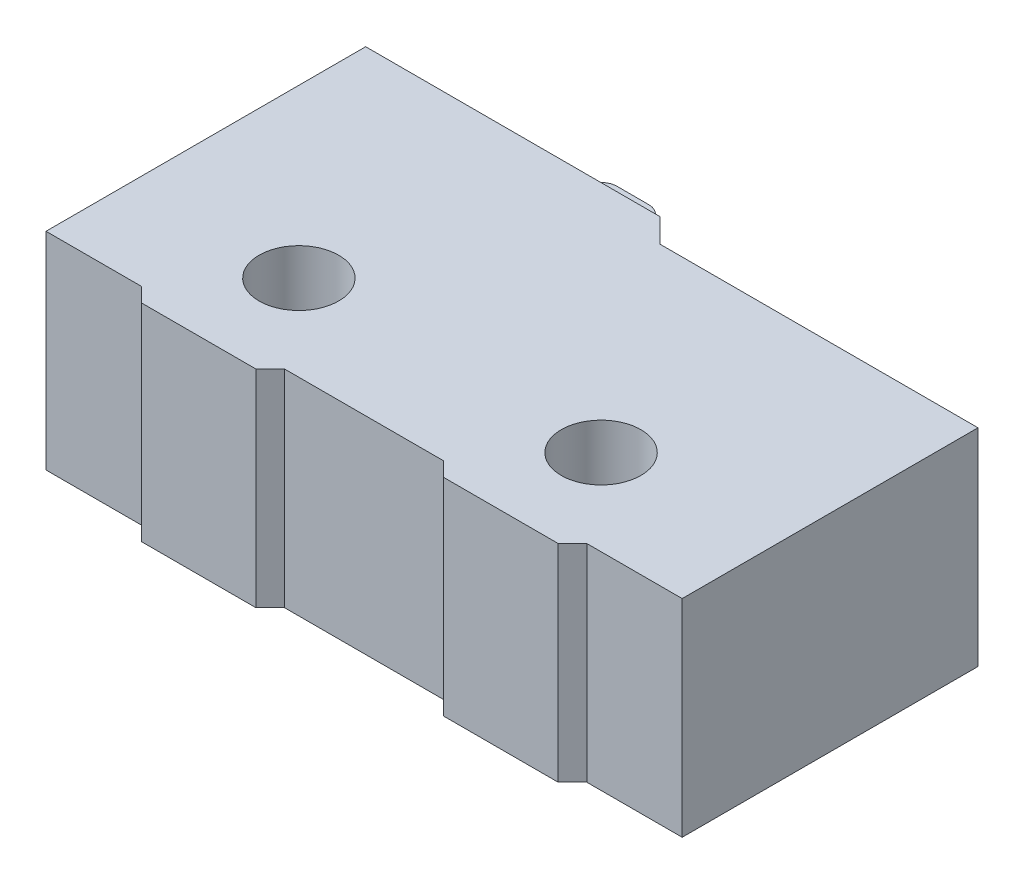
SolidWorks part; units mm, degrees
ref_plane "Front Plane" through (0, 0, 0) normal (0, 0, 1) x (1, 0, 0)
ref_plane "Top Plane" through (0, 0, 0) normal (0, 1, 0) x (1, 0, 0)
ref_plane "Right Plane" through (0, 0, 0) normal (1, 0, 0) x (0, 0, -1)
sketch "스케치1" plane through (0, 0, 0) normal (0, 1, 0) x (1, 0, 0)
  line L1 (-10, 5.25) -> (10, 5.25)
  line L2 (-10, 5.25) -> (-10, -5.25)
  line L3 (-10, -5.25) -> (10, -5.25)
  line L4 (10, 5.25) -> (10, -5.25)
  dimension "D1" = 20
  dimension "D2" = 10.5
  dimension "D3" = 10
  dimension "D4" = 5.25
extrude "보스-돌출1" add sketch "스케치1" along normal blind 6.5
sketch "스케치2" plane through (0, 6.5, 0) normal (0, 1, 0) x (1, 0, 0)
  line L0 (-11.4248, -2.1) -> (49988.5752, -2.1) construction
  line L1 (-4.75, -0.1929) -> (-4.75, -50000.1929) construction
  line L2 (4.75, 1.0289) -> (4.75, -49998.9711) construction
  line L3 (10, -5.25) -> (10, 5.25) construction
  line L4 (-10, 5.25) -> (-10, -5.25) construction
  line L5 (-10, -5.25) -> (10, -5.25) construction
  circle A0 centre (-4.75, -2.1) radius 1.25
  circle A1 centre (4.75, -2.1) radius 1.25
  dimension "D1" = 5.25
  dimension "D2" = 5.25
  dimension "D3" = 3.15
extrude "컷-돌출1" cut sketch "스케치2" against normal blind 6.5
sketch "스케치3" plane through (0, 6.5, 0) normal (0, 1, 0) x (1, 0, 0)
  line L0 (-4.75, -2.1) -> (-4.75, -50002.1) construction
  line L1 (4.75, -2.1) -> (4.75, -50002.1) construction
  line L2 (2.5, -2.5079) -> (2.5, -50002.5079) construction
  line L3 (7, -1.9506) -> (7, -50001.9506) construction
  line L4 (-2.5, -1.9077) -> (-2.5, -50001.9077) construction
  line L6 (-7, -1.8863) -> (-7, -50001.8863) construction
  line L7 (-11.4677, -4.8) -> (49988.5323, -4.8) construction
  line L8 (-10, -5.25) -> (10, -5.25) construction
  line L10 (-11.4463, -4.8) -> (-7, -4.8)
  line L11 (-11.4463, -4.8) -> (-11.4463, -5.8089)
  line L12 (-11.4463, -5.8089) -> (-7, -5.8089)
  line L13 (-7, -4.8) -> (-7, -5.8089)
  line L14 (-2.5, -5.8089) -> (2.5, -5.8089)
  line L15 (-2.5, -5.8089) -> (-2.5, -4.8)
  line L16 (-2.5, -4.8) -> (2.5, -4.8)
  line L17 (2.5, -5.8089) -> (2.5, -4.8)
  line L18 (7, -5.8089) -> (10.6532, -5.8089)
  line L19 (7, -5.8089) -> (7, -4.8)
  line L20 (7, -4.8) -> (10.6532, -4.8)
  line L21 (10.6532, -5.8089) -> (10.6532, -4.8)
  dimension "D1" = 0.45
  dimension "D2" = 4.5
  dimension "D3" = 4.5
  dimension "D4" = 2.25
  dimension "D5" = 2.25
extrude "컷-돌출2" cut sketch "스케치3" against normal blind 6.5
chamfer "모따기1" distance 0.45 angle 45 4 edges at (7, 3.25, 5.25) (2.5, 3.25, 5.25) (-2.5, 3.25, 5.25) (-7, 3.25, 5.25)
sketch "스케치4" plane through (0, 6.5, 0) normal (0, 1, 0) x (1, 0, 0)
  line L0 (-10.7603, 4.5) -> (49989.2397, 4.5) construction
  line L1 (0, 6.602) -> (0, -49993.398) construction
  line L2 (10, 5.25) -> (-10, 5.25) construction
  line L3 (-10, 5.25) -> (-10, -4.8) construction
  line L5 (0, 5.5088) -> (10.3102, 5.5088)
  line L6 (0, 5.5088) -> (0, 4.5)
  line L7 (0, 4.5) -> (10.3102, 4.5)
  line L8 (10.3102, 5.5088) -> (10.3102, 4.5)
  dimension "D1" = 0.75
  dimension "D2" = 10
extrude "컷-돌출3" cut sketch "스케치4" against normal blind 6.5
chamfer "모따기2" distance 0.75 angle 45 1 edges at (0, 3.25, -5.25)
ref_plane "평면1" through (0, 5.25, 0) normal (0, 1, 0) x (1, 0, 0)
sketch "스케치5" plane through (0, 5.25, 0) normal (0, 1, 0) x (1, 0, 0)
  line L0 (-4, 4.1993) -> (-4, -49995.8007) construction
  line L1 (-0.75, 5.25) -> (-10, 5.25) construction
  line L2 (-8.9496, 5.75) -> (49991.0504, 5.75) construction
  line L3 (9.3, 10.1932) -> (9.3, -49989.8068) construction
  line L5 (-10, 5.25) -> (-10, -4.8) construction
  line L9 (-5.1353, 6.65) -> (49994.8647, 6.65) construction
  line L10 (-4, 5.25) -> (-2, 5.25)
  line L11 (-4, 5.25) -> (-4, 6.65)
  line L12 (-4, 6.65) -> (-2, 6.65)
  line L13 (-2, 5.25) -> (-2, 6.65)
  dimension "D1" = 1.4
  dimension "D2" = 6
  dimension "D3" = 2
extrude "보스-돌출2" add sketch "스케치5" against normal blind 4
fillet "필렛1" radius 0.5 2 edges at (-2, 3.25, -6.65) (-4, 3.25, -6.65)
